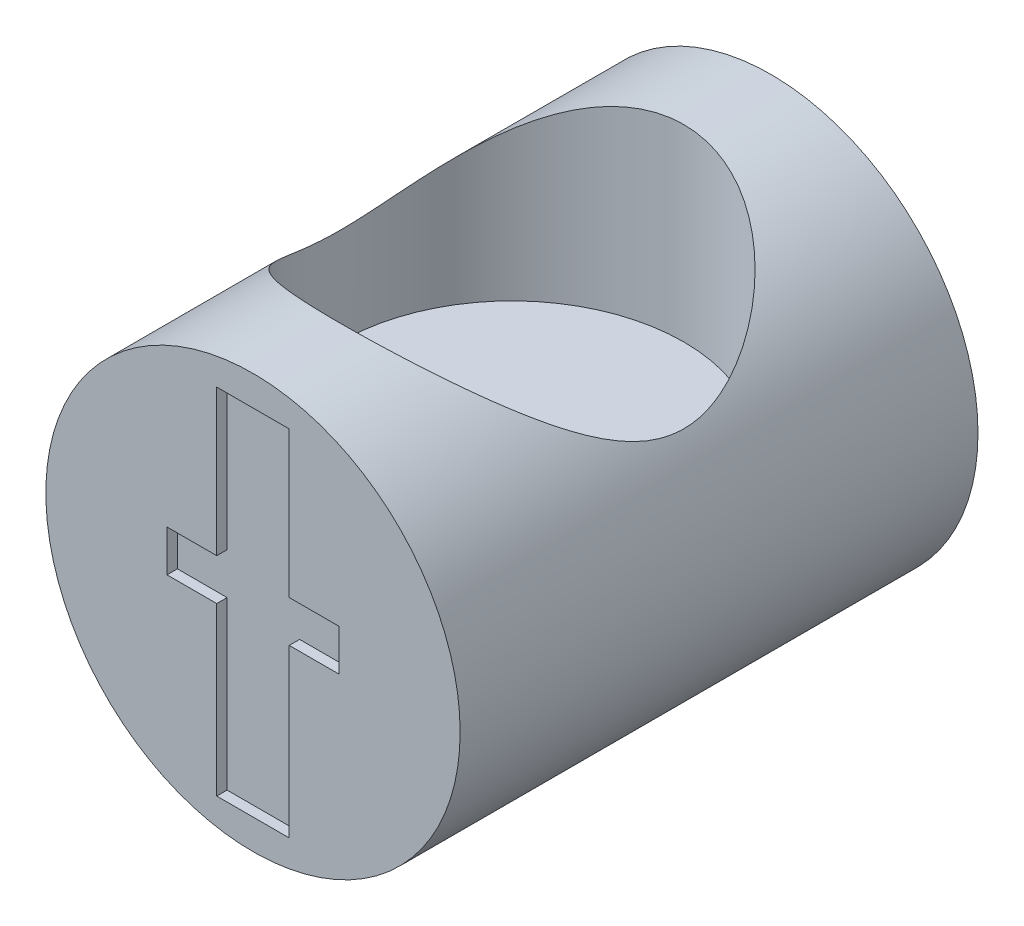
SolidWorks part; units mm, degrees
ref_plane "Alzado" through (0, 0, 0) normal (0, 0, 1) x (1, 0, 0)
ref_plane "Planta" through (0, 0, 0) normal (0, 1, 0) x (1, 0, 0)
ref_plane "Vista lateral" through (0, 0, 0) normal (1, 0, 0) x (0, 0, -1)
sketch "Croquis1" plane through (0, 0, 0) normal (0, 0, 1) x (1, 0, 0)
  circle A0 centre (0, 0) radius 20
  dimension "D1" = 40
extrude "Saliente-Extruir1" add sketch "Croquis1" along normal blind 50
sketch "Croquis2" plane through (0, 0, 50) normal (0, 0, 1) x (1, 0, 0)
  line L0 (0, 0) -> (0, 20) construction
  line L1 (0, 0) -> (0, 20) construction
  circle A0 centre (0, 0) radius 20 construction
sketch3d "Croquis3D1"
  line L0 (0, 0, 50) -> (0, 0, 0) construction
  line L1 (0, 0, 50) -> (0, 0, 0) construction
  line L2 (0, 0, 50) -> (0, 0, 0) construction
  line L3 (0, 0, 0) -> (0, 20.0406, 0) construction
  line L4 (0, 20.0406, 0) -> (0, 20, 50) construction
  circle A0 centre (0, 20.0203, 25) radius 16.6
  point P10 (0, 36.6203, 25)
extrude "Cortar-Extruir2" cut sketch "Croquis3D1" along direction (0, 1, 0) on the side of the normal blind 12.2
sketch "Croquis4" plane through (0, 0, 50) normal (0, 0, 1) x (1, 0, 0)
  line L0 (0, -17.1) -> (0, 17.1) construction
  line L1 (0, 0) -> (0, 20) construction
  line L2 (-20, 0) -> (20, 0) construction
  line L3 (0, 0) -> (-8.3, 0) construction
  line L4 (0, 0) -> (8.3, 0) construction
  line L5 (0, 0) -> (0, 16.2) construction
  line L6 (8.3, 3) -> (3.5, 3)
  line L7 (-8.3, 0) -> (-8.3, -2) construction
  line L8 (8.3, 1) -> (8.3, -1)
  line L9 (8.3, 1) -> (8.3, 3)
  line L10 (-8.3, 1) -> (-8.3, -1)
  line L11 (-8.3, -1) -> (-3.5, -1)
  line L12 (-8.3, 1) -> (-8.3, 3)
  line L13 (-8.3, 3) -> (-3.5, 3)
  line L14 (-3.5, 3) -> (-3.5, 17.1)
  line L15 (-3.5, 17.1) -> (3.5, 17.1)
  line L16 (3.5, 17.1) -> (3.5, 3)
  line L17 (-3.5, -2) -> (-3.5, -17.1)
  line L18 (-3.5, -17.1) -> (3.5, -17.1)
  line L19 (3.5, -17.1) -> (3.5, -2)
  line L20 (3.5, -1) -> (8.3, -1)
  line L21 (-3.5, -2) -> (-3.5, -1)
  line L22 (3.5, -2) -> (3.5, -1)
  circle A0 centre (0, 0) radius 20 construction
  point P11 (0, 0)
  point P18 (0, -2)
  point P20 (-3.5, 0)
  dimension "D1" = 34.2
  dimension "D2" = 34.2
  dimension "D3" = 16.6
  dimension "D4" = 4
  dimension "D5" = 7
  dimension "D7" = 7
extrude "Cortar-Extruir4" cut sketch "Croquis4" against normal blind 1
sketch "Croquis7" plane through (0, 7.8203, 0) normal (0, 1, 0) x (1, 0, 0)
  line L0 (0, -25) -> (0, -50.076) construction
  line L2 (-20, -25) -> (20, -25) construction
  line L3 (-20, 0) -> (-20, -50) construction
  line L4 (20, -50) -> (20, 0) construction
  line L5 (0, -41.6) -> (0, -50.076) construction
  circle A0 centre (0, -25) radius 16.6 construction
  dimension "D1" = 8.476
  dimension "D2" = 16.6
sketch "Croquis9" plane through (0, 0, 49) normal (0, 0, 1) x (1, 0, 0)
  line L0 (0, 0) -> (0, 20) construction
  line L1 (0, 7.8203) -> (0, 20) construction
  line L2 (-20, 7.8203) -> (20, 7.8203) construction
  dimension "D1" = 20
  dimension "D2" = 12.1797
sketch "Croquis10" plane through (0, 7.8203, 0) normal (0, 1, 0) x (1, 0, 0)
  circle A0 centre (0, -25) radius 16.6
extrude "Cortar-Extruir5" cut sketch "Croquis10" against normal blind 6
